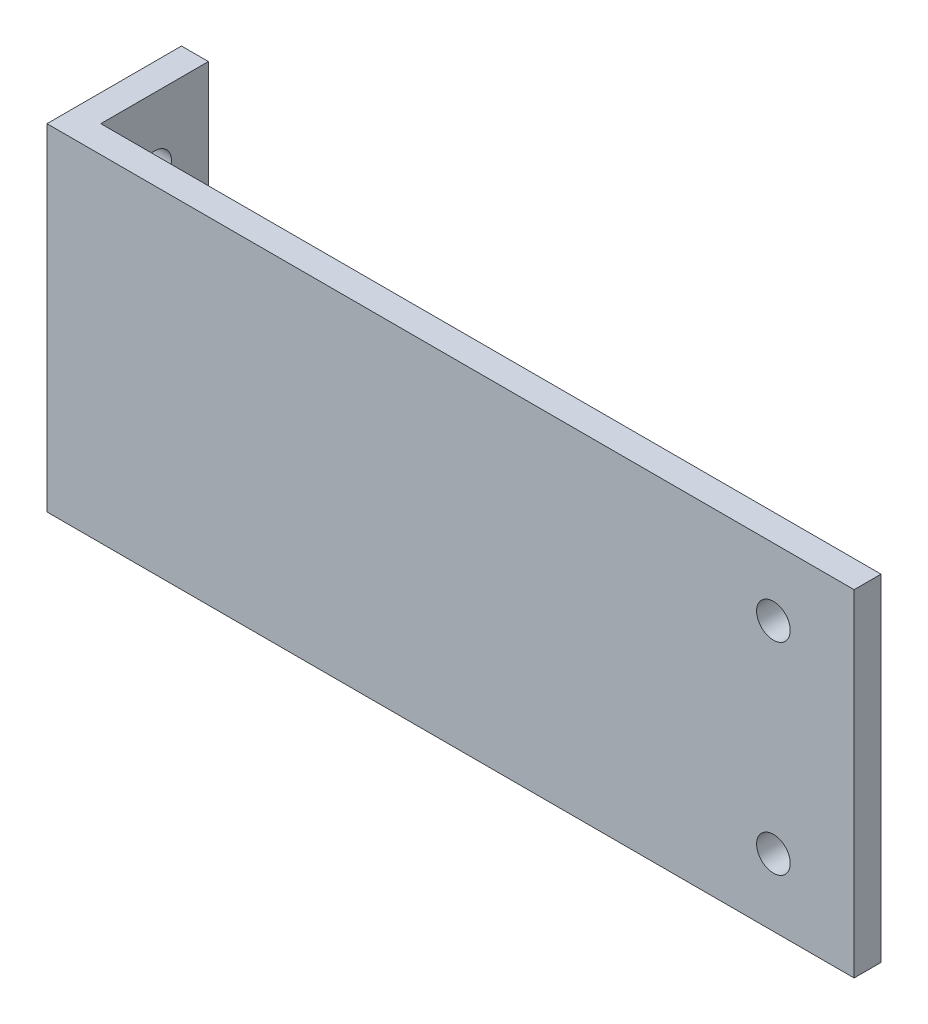
SolidWorks part; units mm, degrees
ref_plane "Спереди" through (0, 0, 0) normal (0, 0, 1) x (1, 0, 0)
ref_plane "Сверху" through (0, 0, 0) normal (0, 1, 0) x (1, 0, 0)
ref_plane "Справа" through (0, 0, 0) normal (1, 0, 0) x (0, 0, -1)
sketch "Эскиз1" plane through (0, 0, 0) normal (0, 1, 0) x (1, 0, 0)
  line L1 (0, 0) -> (120, 0)
  line L2 (0, 0) -> (0, 4)
  line L3 (4, 4) -> (120, 4)
  line L4 (120, 0) -> (120, 4)
  line L6 (0, 4) -> (0, 20)
  line L7 (0, 20) -> (4, 20)
  line L8 (4, 4) -> (4, 20)
  dimension "D1" = 120
  dimension "D2" = 4
  dimension "D3" = 20
  dimension "D4" = 4
extrude "Бобышка-Вытянуть1" add sketch "Эскиз1" along normal blind 50
sketch "Эскиз2" plane through (0, 0, 0) normal (-1, 0, 0) x (0, 0, 1)
  line L0 (-12, 44.9311) -> (-12, 11.555) construction
  line L2 (-20, 0) -> (0, 0) construction
  line L3 (0, 50) -> (0, 0) construction
  circle A0 centre (-12, 40) radius 2.5
  circle A1 centre (-12, 10) radius 2.5
  dimension "D2" = 5
  dimension "D3" = 5
  dimension "D1" = 12
  dimension "D4" = 30
  dimension "D5" = 10
extrude "Вырез-Вытянуть1" cut sketch "Эскиз2" against normal blind 10
sketch "Эскиз3" plane through (0, 0, 0) normal (0, 0, 1) x (1, 0, 0)
  line L0 (108, 46.6766) -> (108, 6.7064) construction
  line L1 (120, 50) -> (120, 0) construction
  line L2 (0, 0) -> (120, 0) construction
  circle A0 centre (108, 40) radius 2.5
  circle A1 centre (108, 10) radius 2.5
  dimension "D2" = 5
  dimension "D3" = 5
  dimension "D1" = 12
  dimension "D4" = 30
  dimension "D5" = 10
extrude "Вырез-Вытянуть2" cut sketch "Эскиз3" against normal blind 10
